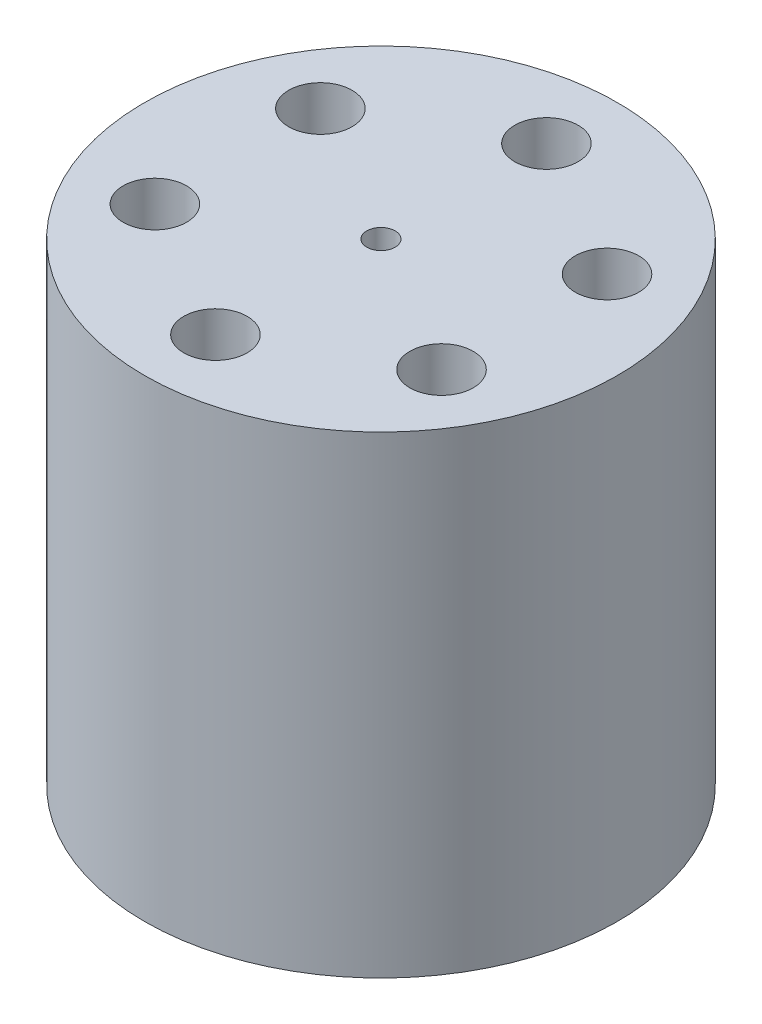
SolidWorks part; units mm, degrees
ref_plane "Front Plane" through (0, 0, 0) normal (0, 0, 1) x (1, 0, 0)
ref_plane "Top Plane" through (0, 0, 0) normal (0, 1, 0) x (1, 0, 0)
ref_plane "Right Plane" through (0, 0, 0) normal (1, 0, 0) x (0, 0, -1)
sketch "Sketch1" plane through (0, 0, 0) normal (0, 1, 0) x (1, 0, 0)
  circle A0 centre (0, 0) radius 25
  circle A1 centre (0, 0) radius 17.5 construction
  circle A2 centre (0, 17.5) radius 3.35
  circle A3 centre (15.1554, 8.75) radius 3.35
  circle A4 centre (15.1554, -8.75) radius 3.35
  circle A5 centre (0, -17.5) radius 3.35
  circle A6 centre (-15.1554, -8.75) radius 3.35
  circle A7 centre (-15.1554, 8.75) radius 3.35
  circle A8 centre (0, 0) radius 1.5
  point P18 (0, 0)
  dimension "D1" = 35
  dimension "D2" = 6.7
  dimension "D4" = 50
  dimension "D5" = 3
  dimension "D3" = 6
extrude "Boss-Extrude1" add sketch "Sketch1" along normal blind 50
